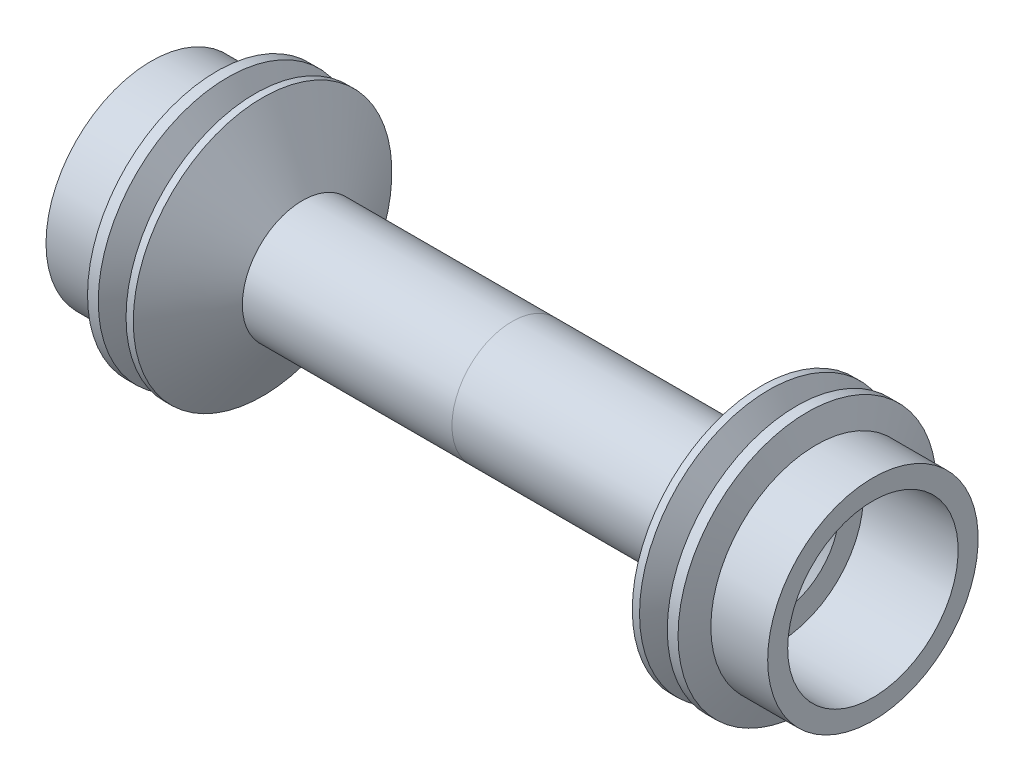
SolidWorks part; units mm, degrees
ref_plane "Front Plane" through (0, 0, 0) normal (0, 0, 1) x (1, 0, 0)
ref_plane "Top Plane" through (0, 0, 0) normal (0, 1, 0) x (1, 0, 0)
ref_plane "Right Plane" through (0, 0, 0) normal (1, 0, 0) x (0, 0, -1)
sketch "Sketch2" plane through (0, 0, 0) normal (0, 0, 1) x (1, 0, 0)
  line L0 (0, 0) -> (0, 28.4375) construction
  line L1 (-19.05, 4.5) -> (-14.05, 4.5) construction
  line L2 (-19.05, 4.5) -> (-19.05, -4.5) construction
  line L3 (-19.05, -4.5) -> (-14.05, -4.5) construction
  line L4 (-14.05, 4.5) -> (-14.05, -4.5) construction
  line L5 (-19.05, 4.5) -> (-14.05, -4.5) construction
  line L6 (-19.05, -4.5) -> (-14.05, 4.5) construction
  line L7 (14.05, 4.5) -> (49.5332, 4.5) construction
  line L8 (14.05, 4.5) -> (14.05, -4.5) construction
  line L9 (14.05, -4.5) -> (49.5332, -4.5) construction
  line L10 (49.5332, 4.5) -> (49.5332, -4.5) construction
  line L11 (14.05, 4.5) -> (49.5332, -4.5) construction
  line L12 (14.05, -4.5) -> (49.5332, 4.5) construction
  line L13 (-19.05, 0) -> (49.5332, 0) construction
  line L14 (-19.05, 5.5562) -> (-16.05, 5.5562)
  line L15 (-16.05, 5.5562) -> (-15.5878, 6.8262)
  line L16 (-15.5878, 6.8262) -> (-15.0207, 6.8262)
  line L17 (-15.0207, 6.8262) -> (-14.2875, 5.5562)
  line L18 (-14.2875, 5.5562) -> (-13.5543, 6.8262)
  line L19 (-13.5543, 6.8262) -> (-13.1733, 6.8262)
  line L20 (-13.1733, 6.8262) -> (-11.0652, 3.175)
  line L21 (-11.0652, 3.175) -> (0, 3.175)
  line L22 (-19.05, 5.5562) -> (-19.05, 4.5)
  line L23 (-19.05, 4.5) -> (-14.05, 4.5)
  line L24 (-14.05, 4.5) -> (-14.05, 0)
  line L25 (-14.05, 0) -> (0, 0)
  line L26 (0, 0) -> (0, 3.175)
  line L27 (-33.5594, -5.5562) -> (-33.5594, 5.5562) construction
  line L28 (-14.2875, 5.5562) -> (-14.2875, 7.68) construction
  line L29 (-14.2875, 5.5562) -> (14.2875, 5.5562) construction
  line L30 (-19.05, 5.5562) -> (19.05, 5.5562) construction
  line L31 (0, 1.6) -> (-6.5, 1.6)
  line L32 (-6.5, 1.6) -> (-8.1, 0)
  line L33 (-6.5, 1.6) -> (-6.5, -1.6) construction
  line L34 (-6.5, 1.6) -> (6.5, 1.6) construction
  line L35 (-14.05, 1.7145) -> (-9.225, 1.7145)
  line L36 (-9.225, 1.7145) -> (-9.225, 0)
  line L37 (-14.05, 3.23) -> (-13.542, 2.722)
  line L38 (-9.225, 1.7145) -> (-22.225, 1.7145) construction
  line L39 (-9.225, 1.7145) -> (-9.225, -1.7145) construction
  line L40 (-9.225, -1.7145) -> (-22.225, -1.7145) construction
  line L41 (-22.225, 1.7145) -> (-22.225, -1.7145) construction
  line L42 (-13.542, 2.722) -> (-13.542, 0)
  point P0 (-16.55, 0)
  point P5 (31.7916, 0)
  point P27 (-33.5594, 0)
  point P28 (-13.3638, 6.8262)
  point P29 (-6.5, 0)
  point P33 (0, 5.5562)
  point P36 (0, 1.6)
  point P48 (-9.225, 0)
  point P51 (0, 5.5562)
  dimension "D1" = 5
  dimension "D3" = 3.175
  dimension "D4" = 11.1125
  dimension "D5" = 9
  dimension "D6" = 60
  dimension "D7" = 60
  dimension "D8" = 1.27
  dimension "D9" = 70
  dimension "D10" = 28.575
  dimension "D11" = 38.1
  dimension "D12" = 0.381
  dimension "D13" = 45
  dimension "D14" = 13
  dimension "D15" = 3.2
  dimension "D16" = 3.429
  dimension "D17" = 3.175
  dimension "D18" = 1.27
  dimension "D19" = 0.508
  dimension "D20" = 45
  dimension "D21" = 13
  dimension "D22" = 3
revolve "Revolve1" add sketch "Sketch2" angle 360 about L13 region at (-17.55, 5.3539, 0)
mirror "Mirror1" about plane through (0, 0, 0) normal (1, 0, 0) of bodies 101
chamfer "Chamfer1" distance 0.508 angle 45 1 edges at (-19.05, 0, 4.5)
